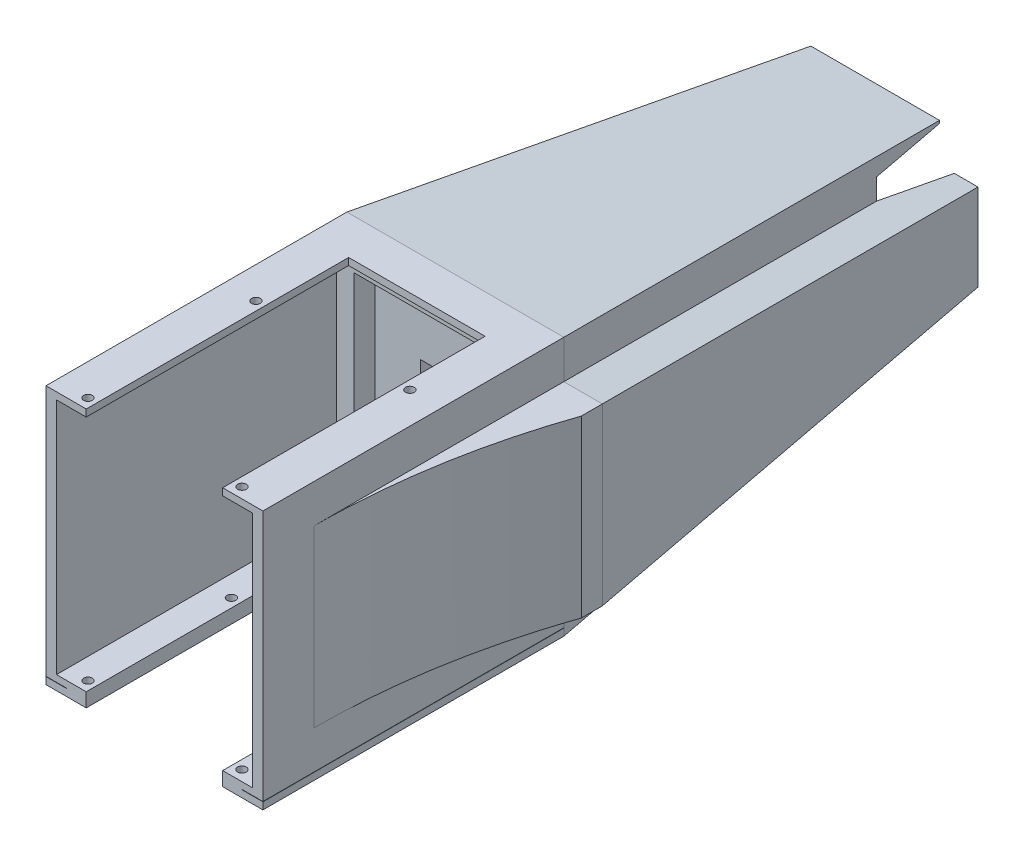
SolidWorks part; units mm, degrees
ref_plane "Front Plane" through (0, 0, 0) normal (0, 0, 1) x (1, 0, 0)
ref_plane "Top Plane" through (0, 0, 0) normal (0, 1, 0) x (1, 0, 0)
ref_plane "Right Plane" through (0, 0, 0) normal (1, 0, 0) x (0, 0, -1)
sketch "Sketch1" plane through (0, 0, 0) normal (0, 0, 1) x (1, 0, 0)
  line L0 (12.5, 12.5) -> (21, 12.5)
  line L1 (-12.5, 18) -> (12.5, 18)
  line L2 (-12.5, 18) -> (-12.5, 12.5)
  line L3 (-12.5, -18) -> (12.5, -18)
  line L4 (12.5, 18) -> (12.5, 12.5)
  line L5 (-12.5, 18) -> (12.5, -18) construction
  line L6 (-12.5, -18) -> (12.5, 18) construction
  line L7 (-21, 12.5) -> (-12.5, 12.5)
  line L8 (-21, 12.5) -> (-21, -12.5)
  line L9 (-21, -12.5) -> (-12.5, -12.5)
  line L10 (21, 12.5) -> (21, -12.5)
  line L11 (-21, 12.5) -> (21, -12.5) construction
  line L12 (-21, -12.5) -> (21, 12.5) construction
  line L13 (-12.5, -12.5) -> (-12.5, -18)
  line L14 (12.5, -12.5) -> (21, -12.5)
  line L15 (12.5, -12.5) -> (12.5, -18)
  point P0 (0, 0)
  point P6 (0, 0)
  dimension "D1" = 25
  dimension "D2" = 36
  dimension "D3" = 25
  dimension "D4" = 42
extrude "Boss-Extrude1" add sketch "Sketch1" along normal blind 3
sketch "Sketch2" plane through (0, 0, 3) normal (0, 0, 1) x (1, 0, 0)
  line L0 (12.5, 12.5) -> (12.5, 18) construction
  line L1 (-12.5, 18) -> (12.5, 18)
  line L2 (-12.5, 18) -> (-12.5, 16)
  line L3 (-12.5, 16) -> (12.5, 16)
  line L4 (12.5, 18) -> (12.5, 16)
  line L5 (-12.5, 18) -> (12.5, 16) construction
  line L6 (-12.5, 16) -> (12.5, 18) construction
  line L7 (12.5, -18) -> (12.5, -12.5) construction
  line L8 (-12.5, -16) -> (12.5, -16)
  line L9 (-12.5, -16) -> (-12.5, -18)
  line L10 (-12.5, -18) -> (12.5, -18)
  line L11 (12.5, -16) -> (12.5, -18)
  line L12 (-12.5, -16) -> (12.5, -18) construction
  line L13 (-12.5, -18) -> (12.5, -16) construction
  line L14 (12.5, 18) -> (-12.5, 18) construction
  point P0 (0, 17)
  point P7 (0, -17)
  dimension "D1" = 2
  dimension "D2" = 2
  dimension "D3" = 0
  dimension "D4" = 0
extrude "Boss-Extrude2" add sketch "Sketch2" along normal blind 40
sketch "Sketch3" plane through (0, 18, 0) normal (0, 1, 0) x (1, 0, 0)
  line L0 (-12.5, -43) -> (-12.5, 0) construction
  line L1 (12.5, -43) -> (12.5, 0) construction
  line L2 (12.5, -43) -> (-12.5, -43) construction
  circle A0 centre (-11, -17.5) radius 0.625
  circle A1 centre (11, -17.5) radius 0.625
  circle A2 centre (-11, -41.5) radius 0.625
  circle A3 centre (11, -41.5) radius 0.625
  dimension "D3" = 1.25
  dimension "D4" = 1.25
  dimension "D6" = 1.25
  dimension "D7" = 1.25
  dimension "D1" = 1.5
  dimension "D2" = 1.5
  dimension "D5" = 24
  dimension "D8" = 1.5
  dimension "D9" = 1.5
  dimension "D10" = 1.5
  dimension "D11" = 1.5
extrude "Cut-Extrude1" cut sketch "Sketch3" against normal blind 3
sketch "Sketch4" plane through (0, -16, 0) normal (0, 1, 0) x (1, 0, 0)
  circle A0 centre (-11, -41.5) radius 0.625
  circle A1 centre (11, -41.5) radius 0.625
  circle A2 centre (-11, -21) radius 0.625
  circle A3 centre (11, -21) radius 0.625
  dimension "D1" = 1.25
  dimension "D2" = 1.25
  dimension "D3" = 20.5
extrude "Cut-Extrude2" cut sketch "Sketch4" against normal blind 3
sketch "Sketch5" plane through (0, 0, 0) normal (0, 0, -1) x (-1, 0, 0)
  line L0 (-12.5, -12.5) -> (-21, -12.5) construction
  line L1 (-21, 12.5) -> (-18, 12.5)
  line L2 (-21, 12.5) -> (-21, -12.5)
  line L3 (-21, -12.5) -> (-18, -12.5)
  line L4 (-18, 12.5) -> (-18, -12.5)
  line L5 (-21, 12.5) -> (-18, -12.5) construction
  line L6 (-21, -12.5) -> (-18, 12.5) construction
  line L7 (12.5, 12.5) -> (21, 12.5) construction
  line L8 (21, -12.5) -> (18, -12.5)
  line L9 (21, -12.5) -> (21, 12.5)
  line L10 (21, 12.5) -> (18, 12.5)
  line L11 (18, -12.5) -> (18, 12.5)
  line L12 (21, -12.5) -> (18, 12.5) construction
  line L13 (21, 12.5) -> (18, -12.5) construction
  point P0 (-19.5, 0)
  point P7 (19.5, 0)
  dimension "D1" = 3
  dimension "D2" = 3
  dimension "D3" = 5.5
  dimension "D4" = 0
sketch "Sketch7" plane through (0, 18, 0) normal (0, 1, 0) x (1, 0, 0)
  line L0 (12.5, -43) -> (-12.5, -43) construction
  line L1 (-9.75, -80.5) -> (9.75, -80.5)
  line L2 (-9.75, -80.5) -> (-9.75, -5.5)
  line L3 (-9.75, -5.5) -> (9.75, -5.5)
  line L4 (9.75, -80.5) -> (9.75, -5.5)
  line L5 (-9.75, -80.5) -> (9.75, -5.5) construction
  line L6 (-9.75, -5.5) -> (9.75, -80.5) construction
  point P0 (0, -43)
  dimension "D1" = 75
  dimension "D2" = 19.5
extrude "Cut-Extrude5" cut sketch "Sketch7" against normal blind 40
sketch "Sketch10" plane through (0, 18, 0) normal (0, 1, 0) x (1, 0, 0)
  line L1 (-12.5, 0) -> (12.5, 0)
  line L2 (-12.5, 0) -> (-12.5, -3)
  line L3 (-12.5, -3) -> (12.5, -3)
  line L4 (12.5, 0) -> (12.5, -3)
extrude "Boss-Extrude4" add sketch "Sketch10" along normal blind 10
sketch "Sketch11" plane through (0, -18, 0) normal (0, -1, 0) x (1, 0, 0)
  line L0 (12.5, 43) -> (12.5, 0) construction
  line L1 (-12.5, 0) -> (12.5, 0)
  line L2 (-12.5, 0) -> (-12.5, 3)
  line L3 (-12.5, 3) -> (12.5, 3)
  line L4 (12.5, 0) -> (12.5, 3)
extrude "Boss-Extrude5" add sketch "Sketch11" along normal blind 10
sketch "Sketch12" plane through (-21, 0, 0) normal (-1, 0, 0) x (0, 0, 1)
  line L0 (3, -12.5) -> (0, -12.5) construction
  line L1 (3, 12.5) -> (0, 12.5)
  line L2 (3, 12.5) -> (3, -12.5)
  line L3 (3, -12.5) -> (0, -12.5)
  line L4 (0, 12.5) -> (0, -12.5)
  line L5 (0, -12.5) -> (0, -28) construction
extrude "Boss-Extrude6" add sketch "Sketch12" along normal blind 10
sketch "Sketch13" plane through (21, 0, 0) normal (1, 0, 0) x (0, 0, -1)
  line L0 (-3, -12.5) -> (0, -12.5) construction
  line L1 (-3, 12.5) -> (0, 12.5)
  line L2 (-3, 12.5) -> (-3, -12.5)
  line L3 (-3, -12.5) -> (0, -12.5)
  line L4 (0, 12.5) -> (0, -12.5)
extrude "Boss-Extrude7" add sketch "Sketch13" along normal blind 10
sketch "Sketch14" plane through (-12.5, 0, 0) normal (-1, 0, 0) x (0, 0, 1)
  line L0 (0, -12.5) -> (0, -28) construction
  line L5 (43, 18) -> (0, 18)
  line L6 (43, 18) -> (43, -17.9581)
  line L7 (43, -17.9581) -> (0, -17.9581)
  line L8 (0, 18) -> (0, -17.9581)
extrude "Boss-Extrude11" add sketch "Sketch14" along normal blind 3
sketch "Sketch15" plane through (12.5, 0, 0) normal (1, 0, 0) x (0, 0, -1)
  line L1 (-43, 18) -> (0, 18)
  line L2 (-43, 18) -> (-43, -17.9581)
  line L3 (-43, -17.9581) -> (0, -17.9581)
  line L4 (0, 18) -> (0, -17.9581)
extrude "Boss-Extrude12" add sketch "Sketch15" along normal blind 3
sketch "Sketch16" plane through (0, 0, 0) normal (0, 0, -1) x (-1, 0, 0)
  line L0 (-15.5, 12.5) -> (-15.5, 18) construction
  line L1 (-11.5, 14) -> (11.5, 14)
  line L2 (-11.5, 14) -> (-11.5, -14)
  line L3 (-11.5, -14) -> (11.5, -14)
  line L4 (11.5, 14) -> (11.5, -14)
  line L5 (-11.5, 14) -> (11.5, -14) construction
  line L6 (-11.5, -14) -> (11.5, 14) construction
  line L7 (15.5, 18) -> (12.5, 18) construction
  point P0 (0, 0)
  dimension "D1" = 4
  dimension "D2" = 4
extrude "Cut-Extrude6" cut sketch "Sketch16" against normal blind 13
fillet "Fillet1" radius 10 1 edges at (31, 12.5, 1.5)
fillet "Fillet2" radius 10 7 edges at (12.5, 28, 1.5) (-12.5, 28, 1.5) (-31, 12.5, 1.5) (12.5, -28, 1.5) (-31, -12.5, 1.5) (-12.5, -28, 1.5) (31, -12.5, 1.5)
sketch "Sketch19" plane through (0, 0, 43) normal (0, 0, 1) x (1, 0, 0)
  line L1 (-14, 16) -> (14, 16)
  line L2 (-14, 16) -> (-14, -16)
  line L3 (-14, -16) -> (14, -16)
  line L4 (14, 16) -> (14, -16)
  line L5 (-14, 16) -> (14, -16) construction
  line L6 (-14, -16) -> (14, 16) construction
  point P0 (0, 0)
  dimension "D1" = 28
extrude "Cut-Extrude9" cut sketch "Sketch19" against normal blind 40
sketch "Sketch20" plane through (0, 0, 3) normal (0, 0, 1) x (1, 0, 0)
  line L0 (-9.75, 18) -> (-15.5, 18) construction
  line L5 (-12.625, 18) -> (12.625, 18)
  line L6 (-12.625, 18) -> (-12.625, 29.8476)
  line L7 (-12.625, 29.8476) -> (12.625, 29.8476)
  line L8 (12.625, 18) -> (12.625, 29.8476)
  line L14 (-12.5, -18) -> (12.5, -18)
  line L15 (-12.5, -18) -> (-12.5, -31.8375)
  line L16 (-12.5, -31.8375) -> (12.5, -31.8375)
  line L17 (12.5, -18) -> (12.5, -31.8375)
extrude "Cut-Extrude11" cut sketch "Sketch20" against normal through all both and the other way through all
sketch "Sketch22" plane through (0, 0, 0) normal (0, 0, -1) x (-1, 0, 0)
  line L1 (21, 12.5) -> (31, 12.5)
  line L2 (21, 12.5) -> (21, -12.5)
  line L3 (21, -12.5) -> (31, -12.5)
  line L4 (31, 12.5) -> (31, -12.5)
  line L5 (-21, 12.5) -> (-31, 12.5)
  line L6 (-21, 12.5) -> (-21, -12.5)
  line L7 (-21, -12.5) -> (-31, -12.5)
  line L8 (-31, 12.5) -> (-31, -12.5)
extrude "Cut-Extrude13" cut sketch "Sketch22" against normal through all both and the other way through all
fillet "Fillet3" radius 100 1 edges at (-15.5, 0, 3) first distance on face at (-15.5, 0.0105, 11.5)
fillet "Fillet4" radius 100 1 edges at (15.5, 0, 3) first distance on face at (18.25, 0, 3)
sketch "Sketch25" plane through (0, 0, 43) normal (0, 0, 1) x (1, 0, 0)
  line L6 (-14, 16) -> (14, 16) construction
  line L7 (-14, 17) -> (14, 17)
  line L13 (-14, 17) -> (-14, 15)
  line L14 (-14, 15) -> (14, 15)
  line L15 (14, 17) -> (14, 15)
  line L16 (-14, 17) -> (14, 15) construction
  line L17 (-14, 15) -> (14, 17) construction
  line L18 (14, -16) -> (14, 16) construction
  line L19 (14, -16) -> (-14, -16) construction
  line L20 (-14, -15) -> (14, -15)
  line L21 (-14, -15) -> (-14, -17)
  line L22 (-14, -17) -> (14, -17)
  line L23 (14, -15) -> (14, -17)
  line L24 (-14, -15) -> (14, -17) construction
  line L25 (-14, -17) -> (14, -15) construction
  point P0 (0, 16)
  point P9 (0, -16)
  dimension "D1" = 1
  dimension "D2" = 2
extrude "Cut-Extrude17" cut sketch "Sketch25" against normal blind 40
sketch "Sketch27" plane through (0, -18, 0) normal (0, -1, 0) x (1, 0, 0)
  line L0 (-15.5, 43) -> (-9.75, 43)
  line L1 (-9.75, 43) -> (-9.75, 5.5)
  line L2 (9.75, 5.5) -> (-9.75, 5.5) construction
  line L3 (-9.75, 5.5) -> (-9.75, 43) construction
  line L4 (-9.75, 5.5) -> (9.75, 5.5)
  line L5 (9.75, 5.5) -> (9.75, 43)
  line L6 (9.75, 43) -> (15.5, 43)
  line L7 (15.5, 43) -> (15.5, 0)
  line L8 (15.5, 0) -> (-15.5, 0)
  line L9 (-15.5, 0) -> (-15.5, 43)
  circle A0 centre (-11, 41.5) radius 0.625
  circle A1 centre (-11, 21) radius 0.625
  circle A2 centre (11, 21) radius 0.625
  circle A3 centre (11, 41.5) radius 0.625
extrude "Boss-Extrude14" add sketch "Sketch27" along normal blind 1
sketch "Sketch30" plane through (0, 0, -60) normal (0, 0, -1) x (-1, 0, 0)
  line L1 (-4, 1.5) -> (4, 1.5)
  line L2 (-4, 1.5) -> (-4, -1.5)
  line L3 (-4, -1.5) -> (4, -1.5)
  line L4 (4, 1.5) -> (4, -1.5)
  line L5 (-4, 1.5) -> (4, -1.5) construction
  line L6 (-4, -1.5) -> (4, 1.5) construction
  point P0 (0, 0)
  dimension "D1" = 8
  dimension "D2" = 3
sketch "Sketch31" plane through (0, 0, 0) normal (0, 0, -1) x (-1, 0, 0)
  line L0 (-15.5, 18) -> (15.5, 18)
  line L1 (15.5, 18) -> (-15.5, 18) construction
  line L2 (15.5, 18) -> (15.5, 12.5) construction
  line L3 (15.5, 18) -> (15.5, 12.5)
  line L4 (15.5, 12.5) -> (21, 12.5) construction
  line L5 (21, 12.5) -> (15.5, 12.5) construction
  line L6 (15.5, 12.5) -> (21, 12.5)
  line L7 (21, 12.5) -> (21, -12.5)
  line L8 (21, -12.5) -> (15.5, -12.5)
  line L9 (15.5, -12.5) -> (15.5, -19)
  line L10 (15.5, -19) -> (-15.5, -19)
  line L11 (-15.5, -19) -> (-15.5, -12.5)
  line L12 (-15.5, -12.5) -> (-21, -12.5)
  line L13 (-21, -12.5) -> (-21, 12.5)
  line L14 (-21, 12.5) -> (-15.5, 12.5)
  line L15 (-15.5, 12.5) -> (-15.5, 18)
  line L31 (-5, 5) -> (5, 5)
  line L32 (-5, 5) -> (-5, -5)
  line L33 (-5, -5) -> (5, -5)
  line L34 (5, 5) -> (5, -5)
  line L35 (-5, 5) -> (5, -5) construction
  line L36 (-5, -5) -> (5, 5) construction
  point P39 (0, 0)
  dimension "D11" = 10
  dimension "D12" = 10
extrude "Boss-Extrude16" add sketch "Sketch31" along normal blind 60 draft 6
